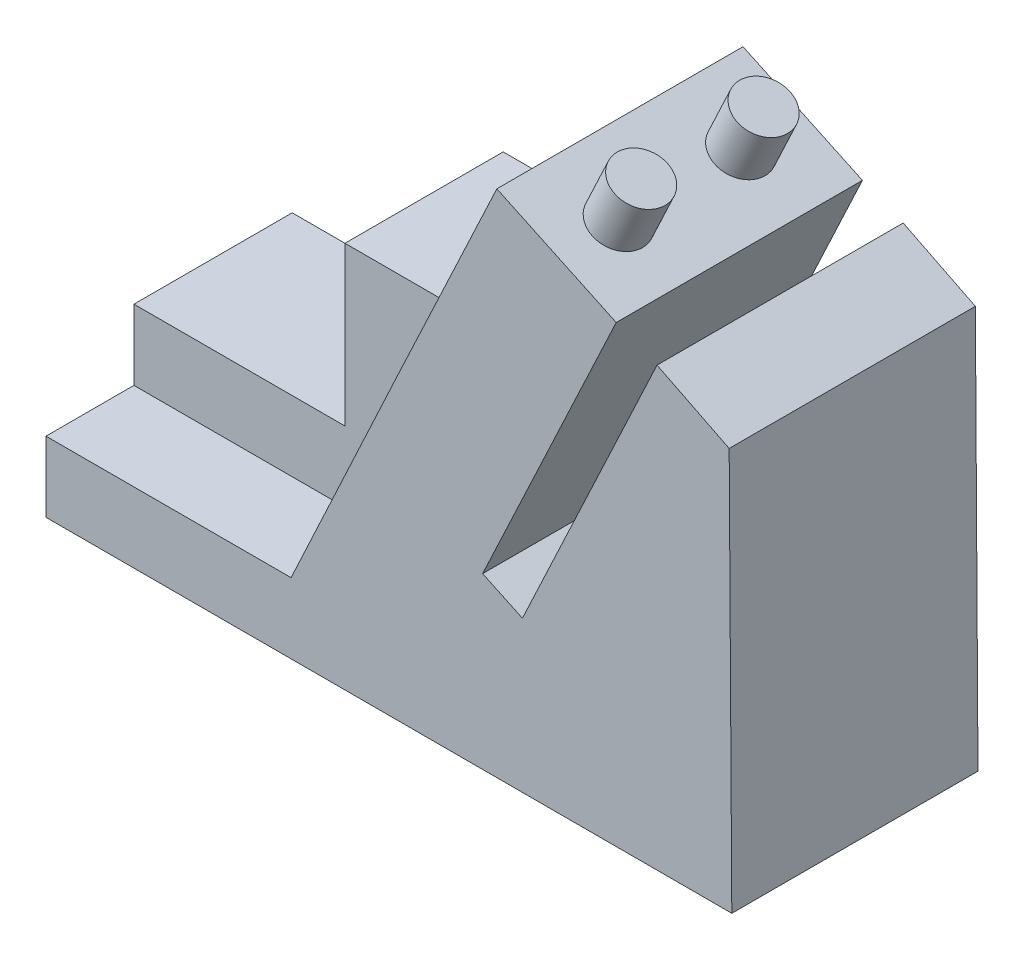
SolidWorks part; units mm, degrees
ref_plane "Alzado" through (0, 0, 0) normal (0, 0, 1) x (1, 0, 0)
ref_plane "Planta" through (0, 0, 0) normal (0, 1, 0) x (1, 0, 0)
ref_plane "Vista lateral" through (0, 0, 0) normal (1, 0, 0) x (0, 0, -1)
sketch "Croquis1" plane through (0, 0, 0) normal (0, 0, 1) x (1, 0, 0)
  line L0 (0, 0) -> (78, 0)
  line L1 (0, 0) -> (0, 16)
  line L2 (0, 16) -> (24, 16)
  line L3 (24, 16) -> (24, 34)
  line L4 (24, 34) -> (40, 34)
  line L5 (0, 8) -> (27.876, 8)
  line L6 (27.876, 8) -> (40, 34)
  line L7 (64.8528, 51.6211) -> (51.2767, 58)
  line L8 (64.8528, 51.6211) -> (49.6604, 19.2875)
  line L9 (49.6604, 19.2875) -> (54.1858, 17.1613)
  line L10 (54.1858, 17.1613) -> (69.4951, 49.7438)
  line L11 (69.4951, 49.7438) -> (77.6995, 45.6391)
  line L12 (77.6995, 45.6391) -> (78, 0)
  line L13 (51.2767, 58) -> (40, 34)
  point P9 (59.1528, 45.2395)
  point P16 (53.2716, 17.2303)
  dimension "D3" = 24
  dimension "D6" = 65
  dimension "D8" = 58
  dimension "D1" = 78
  dimension "D2" = 16
  dimension "D4" = 18
  dimension "D5" = 16
  dimension "D7" = 15
  dimension "D9" = 26.4228
  dimension "D10" = 5
  dimension "D11" = 36
  dimension "D12" = 45.6391
  dimension "D13" = 9.1739
  dimension "D14" = 37.7753
extrude "Saliente-Extruir1" add sketch "Croquis1" along normal blind 18 contours L5 L6 L4 L3 L2 L1 region at (0.4771, 12, 0)
extrude "Saliente-Extruir2" add sketch "Croquis1<3>" along normal blind 28 contours L7 L13 L6 L5 L1 L0 L12 L11 L10 L9 L8 region at (0.972, 4, 0)
sketch "Croquis1<3>" plane through (0, 0, 0) normal (0, 0, 1) x (1, 0, 0) same geometry as "Croquis1"
sketch "Croquis3" plane through (31.5968, 67.2469, 0) normal (0.4253, 0.9051, 0) x (0.9051, -0.4253, 0)
  line L0 (36.7441, 0) -> (21.7441, 0) construction
  line L1 (21.7441, -28) -> (21.7441, 0) construction
  line L2 (36.7441, -28) -> (21.7441, -28) construction
  line L3 (21.8277, -28) -> (21.8277, -18) construction
  circle A0 centre (29.2441, -7) radius 3
  circle A1 centre (29.3277, -21) radius 3
  dimension "D1" = 6
  dimension "D2" = 6
  dimension "D3" = 7
  dimension "D4" = 7.5
  dimension "D5" = 7
  dimension "D6" = 7.5
extrude "Saliente-Extruir3" add sketch "Croquis3" along normal blind 6
